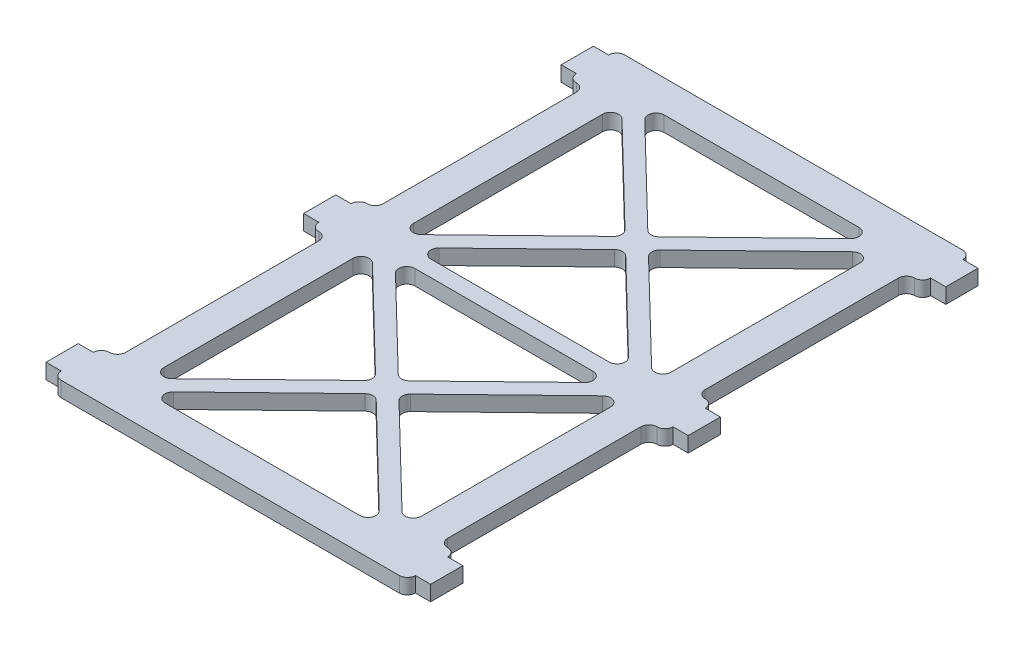
SolidWorks part; units mm, degrees
ref_plane "Front Plane" through (0, 0, 0) normal (0, 0, 1) x (1, 0, 0)
ref_plane "Top Plane" through (0, 0, 0) normal (0, 1, 0) x (1, 0, 0)
ref_plane "Right Plane" through (0, 0, 0) normal (1, 0, 0) x (0, 0, -1)
sketch "Sketch1" plane through (0, 34.29, 0) normal (0, 1, 0) x (1, 0, 0)
  line L0 (35.1028, 190.5) -> (38.1, 190.5) construction
  line L1 (0, -190.5) -> (0, 187.198) construction
  line L2 (38.1028, 187.198) -> (35.1028, 187.198) construction
  line L3 (35.1028, -190.5) -> (38.1, -190.5) construction
  line L5 (-31.75, 65.0875) -> (31.75, 65.0875)
  line L6 (-31.75, 65.0875) -> (-31.75, 176.2125)
  line L7 (-31.75, 176.2125) -> (31.75, 176.2125)
  line L8 (31.75, 65.0875) -> (31.75, 176.2125)
  line L9 (-31.75, 65.0875) -> (31.75, 176.2125) construction
  line L10 (-31.75, 176.2125) -> (31.75, 65.0875) construction
  point P0 (0, 120.65)
  point P12 (0, -1.651)
  point P13 (0, 0)
  point P14 (0, 0)
  point P15 (0, 0)
  point P16 (0, 0)
  point P17 (0, 0)
  point P20 (0, 0)
  dimension "D1" = 111.125
  dimension "D2" = 63.5
  dimension "D3" = 14.2875
extrude "Boss-Extrude1" add sketch "Sketch1" along normal mid plane 3 contours L7 L8 L5 L6
sketch "Sketch2" plane through (0, 35.79, 0) normal (0, 1, 0) x (1, 0, 0)
  line L0 (0, 176.2125) -> (0, 65.0186) construction
  line L1 (-31.75, 176.2125) -> (31.75, 176.2125) construction
  line L2 (31.75, 120.65) -> (-31.75, 120.65) construction
  line L3 (31.75, 65.0875) -> (31.75, 176.2125) construction
  line L4 (-31.75, 65.0875) -> (-31.75, 176.2125) construction
  line L5 (-34.925, 176.2125) -> (-31.75, 166.6875) construction
  line L6 (34.925, 166.6875) -> (31.75, 166.6875)
  line L7 (34.925, 166.6875) -> (34.925, 176.2125)
  line L8 (34.925, 176.2125) -> (31.75, 176.2125)
  line L9 (31.75, 166.6875) -> (31.75, 176.2125)
  line L10 (34.925, 166.6875) -> (31.75, 176.2125) construction
  line L11 (34.925, 176.2125) -> (31.75, 166.6875) construction
  line L12 (-34.925, 166.6875) -> (-31.75, 176.2125) construction
  line L13 (-31.75, 166.6875) -> (-31.75, 176.2125)
  line L14 (-34.925, 176.2125) -> (-31.75, 176.2125)
  line L15 (-34.925, 166.6875) -> (-34.925, 176.2125)
  line L16 (-34.925, 166.6875) -> (-31.75, 166.6875)
  line L17 (34.925, 115.8875) -> (31.75, 115.8875)
  line L18 (34.925, 115.8875) -> (34.925, 125.4125)
  line L19 (34.925, 125.4125) -> (31.75, 125.4125)
  line L20 (31.75, 115.8875) -> (31.75, 125.4125)
  line L21 (34.925, 115.8875) -> (31.75, 125.4125) construction
  line L22 (34.925, 125.4125) -> (31.75, 115.8875) construction
  line L23 (-31.75, 115.8875) -> (-31.75, 125.4125)
  line L24 (-34.925, 125.4125) -> (-31.75, 125.4125)
  line L25 (-34.925, 115.8875) -> (-34.925, 125.4125)
  line L26 (-34.925, 115.8875) -> (-31.75, 115.8875)
  line L27 (-34.925, 125.4125) -> (-31.75, 115.8875) construction
  line L28 (-34.925, 115.8875) -> (-31.75, 125.4125) construction
  line L29 (34.925, 65.0875) -> (31.75, 65.0875)
  line L30 (34.925, 65.0875) -> (34.925, 74.6125)
  line L31 (34.925, 74.6125) -> (31.75, 74.6125)
  line L32 (31.75, 65.0875) -> (31.75, 74.6125)
  line L33 (34.925, 65.0875) -> (31.75, 74.6125) construction
  line L34 (34.925, 74.6125) -> (31.75, 65.0875) construction
  line L35 (-31.75, 65.0875) -> (-31.75, 74.6125)
  line L36 (-34.925, 74.6125) -> (-31.75, 74.6125)
  line L37 (-34.925, 65.0875) -> (-34.925, 74.6125)
  line L38 (-34.925, 65.0875) -> (-31.75, 65.0875)
  line L39 (-34.925, 74.6125) -> (-31.75, 65.0875) construction
  line L40 (-34.925, 65.0875) -> (-31.75, 74.6125) construction
  point P11 (33.3375, 171.45)
  point P21 (-33.3375, 171.45)
  point P22 (0, 0)
  point P24 (33.3375, 120.65)
  point P33 (-33.3375, 120.65)
  point P34 (33.3375, 69.85)
  point P43 (-33.3375, 69.85)
  dimension "D1" = 3.175
  dimension "D2" = 9.525
  dimension "D3" = 3
extrude "Boss-Extrude2" add sketch "Sketch2" against normal up to surface (3 mm away) up to face at (0, 32.79, -120.65)
sketch "Sketch4" plane through (0, 35.79, 0) normal (0, 1, 0) x (1, 0, 0)
  line L0 (31.75, 125.4125) -> (31.75, 166.6875) construction
  line L1 (-25.4, 169.8625) -> (25.4, 169.8625)
  line L2 (-25.4, 169.8625) -> (-25.4, 71.4375)
  line L3 (-25.4, 71.4375) -> (25.4, 71.4375)
  line L4 (25.4, 169.8625) -> (25.4, 71.4375)
  line L5 (-25.4, 169.8625) -> (25.4, 71.4375) construction
  line L6 (-25.4, 71.4375) -> (25.4, 169.8625) construction
  line L7 (-31.75, 125.4125) -> (-31.75, 166.6875) construction
  line L8 (-34.925, 176.2125) -> (34.925, 176.2125) construction
  line L9 (-34.925, 65.0875) -> (34.925, 65.0875) construction
  line L10 (-25.4, 120.65) -> (25.4, 120.65) construction
  line L11 (25.4, 120.65) -> (-25.4, 169.8625) construction
  line L12 (25.4, 120.65) -> (-25.4, 71.4375) construction
  line L13 (-25.4, 120.65) -> (25.4, 169.8625) construction
  line L14 (25.4, 71.4375) -> (-25.4, 120.65) construction
  line L15 (-25.4, 119.0625) -> (25.4, 119.0625)
  line L16 (-25.4, 122.2375) -> (25.4, 122.2375)
  line L17 (26.5046, 72.5777) -> (-23.1184, 120.65)
  line L18 (-23.1184, 120.65) -> (26.5046, 168.7223)
  line L19 (27.6816, 120.65) -> (-24.2954, 70.2973)
  line L20 (27.6816, 120.65) -> (-24.2954, 171.0027)
  line L21 (24.2954, 70.2973) -> (-27.6816, 120.65)
  line L22 (-27.6816, 120.65) -> (24.2954, 171.0027)
  line L23 (23.1184, 120.65) -> (-26.5046, 72.5777)
  line L24 (23.1184, 120.65) -> (-26.5046, 168.7223)
  point P0 (0, 120.65)
  dimension "D1" = 6.35
  dimension "D2" = 6.35
  dimension "D3" = 6.35
  dimension "D4" = 6.35
  dimension "D5" = 1.5875
  dimension "D6" = 1.5875
  dimension "D7" = 1.5875
  dimension "D8" = 1.5875
extrude "Cut-Extrude1" cut sketch "Sketch4" against normal blind 3 contours L15 L19 L17 L4 | L3 L21 L19 | L23 L21 L15 L2 | L23 L15 L17 | L16 L24 L18 | L20 L16 L4 L18 | L20 L22 L1 | L22 L24 L2 L16 region at (0, 35.79, -162.3972) region at (-17.6939, 35.79, -145.2563) region at (17.6939, 35.79, -145.2563) region at (0, 35.79, -129.1737) region at (-17.6939, 35.79, -96.0438) region at (0, 35.79, -112.1263) region at (17.6939, 35.79, -96.0438) region at (0, 35.79, -78.9028)
fillet "Fillet1" radius 1.5875 44 edges at (-21.4797, 34.29, -119.0625) (21.4797, 34.29, -119.0625) (0, 34.29, -98.254) (-25.4, 34.29, -118.4397) (-2.2816, 34.29, -96.0438) (-25.4, 34.29, -73.6478) (25.4, 34.29, -167.6522) (25.4, 34.29, -122.8603) (2.2816, 34.29, -145.2563) (23.1184, 34.29, -169.8625) (0, 34.29, -147.4665) (-23.1184, 34.29, -169.8625) (2.2816, 34.29, -96.0438) (25.4, 34.29, -118.4397) (25.4, 34.29, -73.6478) (34.925, 34.29, -65.0875) (34.925, 34.29, -74.6125) (31.75, 34.29, -74.6125) (31.75, 34.29, -115.8875) (34.925, 34.29, -115.8875) (34.925, 34.29, -125.4125) (31.75, 34.29, -125.4125) (31.75, 34.29, -166.6875) (34.925, 34.29, -166.6875) (34.925, 34.29, -176.2125) (-34.925, 34.29, -166.6875) (-31.75, 34.29, -166.6875) (-31.75, 34.29, -125.4125) (-34.925, 34.29, -125.4125) (-34.925, 34.29, -115.8875) (-31.75, 34.29, -115.8875) (-31.75, 34.29, -74.6125) (-34.925, 34.29, -74.6125) (-34.925, 34.29, -65.0875) (-25.4, 34.29, -122.8603) (-25.4, 34.29, -167.6522) (-2.2816, 34.29, -145.2563) (-23.1184, 34.29, -71.4375) (0, 34.29, -93.8335) (23.1184, 34.29, -71.4375) (-21.4797, 34.29, -122.2375) (0, 34.29, -143.046) (21.4797, 34.29, -122.2375) (-34.925, 34.29, -176.2125)
sketch "Sketch5" plane through (0, 35.79, 0) normal (0, 1, 0) x (1, 0, 0)
  line L0 (34.925, 168.275) -> (34.925, 174.625) construction
  line L1 (37.925, 168.275) -> (34.925, 168.275)
  line L2 (37.925, 168.275) -> (37.925, 174.625)
  line L3 (37.925, 174.625) -> (34.925, 174.625)
  line L4 (34.925, 168.275) -> (34.925, 174.625)
  line L5 (37.925, 168.275) -> (34.925, 174.625) construction
  line L6 (37.925, 174.625) -> (34.925, 168.275) construction
  line L7 (34.925, 168.275) -> (34.925, 174.625) construction
  line L8 (34.925, 171.45) -> (36.425, 171.45) construction
  line L9 (0, 196.0278) -> (0, 0) construction
  line L10 (-34.925, 171.45) -> (-36.425, 171.45) construction
  line L11 (-37.925, 174.625) -> (-34.925, 168.275) construction
  line L12 (-37.925, 168.275) -> (-34.925, 174.625) construction
  line L13 (-34.925, 168.275) -> (-34.925, 174.625)
  line L14 (-37.925, 174.625) -> (-34.925, 174.625)
  line L15 (-37.925, 168.275) -> (-37.925, 174.625)
  line L16 (-37.925, 168.275) -> (-34.925, 168.275)
  line L17 (37.925, 117.475) -> (34.925, 117.475)
  line L18 (37.925, 117.475) -> (37.925, 123.825)
  line L19 (37.925, 123.825) -> (34.925, 123.825)
  line L20 (34.925, 117.475) -> (34.925, 123.825)
  line L21 (37.925, 117.475) -> (34.925, 123.825) construction
  line L22 (37.925, 123.825) -> (34.925, 117.475) construction
  line L23 (34.925, 120.65) -> (36.425, 120.65) construction
  line L24 (-34.925, 117.475) -> (-34.925, 123.825)
  line L25 (-37.925, 123.825) -> (-34.925, 123.825)
  line L26 (-37.925, 117.475) -> (-37.925, 123.825)
  line L27 (-37.925, 117.475) -> (-34.925, 117.475)
  line L28 (-34.925, 120.65) -> (-36.425, 120.65) construction
  line L29 (-37.925, 123.825) -> (-34.925, 117.475) construction
  line L30 (-37.925, 117.475) -> (-34.925, 123.825) construction
  line L31 (37.925, 66.675) -> (34.925, 66.675)
  line L32 (37.925, 66.675) -> (37.925, 73.025)
  line L33 (37.925, 73.025) -> (34.925, 73.025)
  line L34 (34.925, 66.675) -> (34.925, 73.025)
  line L35 (37.925, 66.675) -> (34.925, 73.025) construction
  line L36 (37.925, 73.025) -> (34.925, 66.675) construction
  line L37 (34.925, 69.85) -> (36.425, 69.85) construction
  line L38 (-34.925, 66.675) -> (-34.925, 73.025)
  line L39 (-37.925, 73.025) -> (-34.925, 73.025)
  line L40 (-37.925, 66.675) -> (-37.925, 73.025)
  line L41 (-37.925, 66.675) -> (-34.925, 66.675)
  line L42 (-34.925, 69.85) -> (-36.425, 69.85) construction
  line L43 (-37.925, 73.025) -> (-34.925, 66.675) construction
  line L44 (-37.925, 66.675) -> (-34.925, 73.025) construction
  line L45 (-36.425, 171.45) -> (-36.425, 120.65) construction
  point P0 (36.425, 171.45)
  point P7 (36.425, 120.65)
  point P21 (-36.425, 171.45)
  point P35 (-36.425, 120.65)
  point P36 (36.425, 69.85)
  point P49 (-36.425, 69.85)
  dimension "D1" = 3
  dimension "D2" = 6.35
  dimension "D4" = 50.8
  dimension "D3" = 3
extrude "Boss-Extrude3" add sketch "Sketch5" against normal up to surface (3 mm away) up to face at (0, 32.79, -129.6767)
